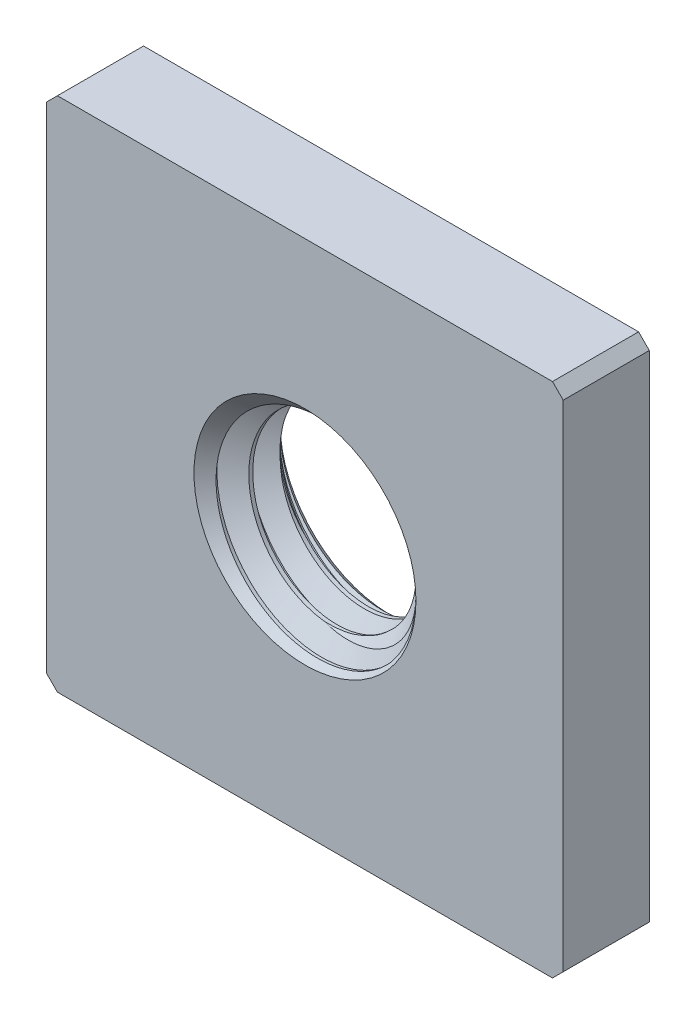
SolidWorks part; units mm, degrees
ref_plane "Front Plane" through (0, 0, 0) normal (0, 0, 1) x (1, 0, 0)
ref_plane "Top Plane" through (0, 0, 0) normal (0, 1, 0) x (1, 0, 0)
ref_plane "Right Plane" through (0, 0, 0) normal (1, 0, 0) x (0, 0, -1)
sketch "Sketch1" plane through (0, 0, 0) normal (0, 0, 1) x (1, 0, 0)
  line L1 (19.05, 19.05) -> (-19.05, 19.05) construction
  line L2 (19.05, 19.05) -> (19.05, -19.05) construction
  line L3 (19.05, -19.05) -> (-19.05, -19.05) construction
  line L4 (-19.05, 19.05) -> (-19.05, -19.05) construction
  line L5 (19.05, 19.05) -> (-19.05, -19.05) construction
  line L6 (19.05, -19.05) -> (-19.05, 19.05) construction
  point P0 (0, 0)
  dimension "For Leg Outer Length" = 38.1
  dimension "For Leg Outer Width" = 38.1
sketch "Sketch2" plane through (0, 0, 0) normal (0, 1, 0) x (1, 0, 0)
  line L0 (0, 3.175) -> (0, -3.175) construction
  line L2 (7.9375, -3.175) -> (-7.9375, -3.175) construction
  line L3 (-19.05, 3.175) -> (19.05, 3.175) construction
  line L4 (-19.05, -3.175) -> (19.05, -3.175) construction
  line L6 (8.1875, -3.0307) -> (8.1875, -5.3398) construction
  line L7 (8.1875, -5.3398) -> (6.1877, -4.1852) construction
  line L8 (6.1877, -4.1852) -> (8.1875, -3.0307) construction
  line L9 (6.1877, -4.1852) -> (6.4377, -4.1852) construction
  line L10 (8.1875, -4.1852) -> (7.9375, -4.1852) construction
  line L11 (6.4377, -4.3295) -> (6.4377, -4.0409) construction
  line L12 (7.9375, -5.1955) -> (7.9375, -3.175) construction
  line L13 (8.0625, -5.2676) -> (8.0625, -3.1028) construction
  point P4 (0, 0)
  point P8 (0, -3.175)
  point P11 (0, 3.175)
  point P14 (0, -3.175)
  point P26 (6.4377, -4.1852)
  point P29 (7.9375, -4.1852)
  point P32 (8.0625, -4.1852)
  dimension "Thread Diameter" = 15.875
  dimension "Height" = 6.35
  dimension "Thread Pitch" = 2.3091
  dimension "D1" = 0.2886
sketch "Sketch3" plane through (0, 0, 0) normal (0, 0, 1) x (1, 0, 0)
  line L0 (-19.05, 0) -> (19.05, 0) construction
  line L1 (19.05, 19.05) -> (-19.05, 19.05)
  line L2 (19.05, 19.05) -> (19.05, -19.05)
  line L3 (19.05, -19.05) -> (-19.05, -19.05)
  line L4 (-19.05, 19.05) -> (-19.05, -19.05)
  line L5 (19.05, 19.05) -> (-19.05, -19.05) construction
  line L6 (19.05, -19.05) -> (-19.05, 19.05) construction
  circle A0 centre (0, 0) radius 7.9375
  point P0 (0, 0)
extrude "Boss-Extrude1" add sketch "Sketch3" against normal up to vertex (3.175 mm away) from vertex up to point (0, 0, -3.175) starting at point (0, 0, 3.175)
chamfer "Chamfer1" distance 0.7937 angle 45 4 edges at (-19.05, 19.05, 0) (19.05, 19.05, 0) (19.05, -19.05, 0) (-19.05, -19.05, 0)
sketch "Sketch4" plane through (0, 0, 3.175) normal (0, 0, 1) x (1, 0, 0)
  circle A0 centre (0, 0) radius 7.9375 construction
  circle A1 centre (0, 0) radius 7.9375
curve "Helix/Spiral1" pitch 2.3091 height 8.6591 radius 7.9375 centre (0, 0, 3.175) axis (0, 0, -1) start towards (1, 0, 0)
sketch "Sketch5" plane through (0, 0, 0) normal (0, 1, 0) x (1, 0, 0)
  line L0 (8.0625, -3.1028) -> (8.0625, -5.2676)
  line L1 (8.0625, -5.2676) -> (6.4377, -4.3295)
  line L2 (6.4377, -4.3295) -> (6.4377, -4.0409)
  line L3 (6.4377, -4.0409) -> (8.0625, -3.1028)
sweep "Sweep1" add profiles "Sketch5" path "Helix/Spiral1"
sketch "Sketch6" plane through (0, 0, 3.175) normal (0, 0, 1) x (1, 0, 0)
  circle A0 centre (0, 0) radius 8.1875
extrude "Cut-Extrude1" cut sketch "Sketch6" against normal through all draft 45 and the other way through all
extrude "Cut-Extrude2" cut sketch "Sketch6<2>" against normal through all and the other way through all draft 45 from surface starting at face at (0, 0, -3.175)
sketch "Sketch6<2>" plane through (0, 0, 3.175) normal (0, 0, 1) x (1, 0, 0) same geometry as "Sketch6"
equation "\"D1@Sketch2\"=\"Thread Pitch@Sketch2\"/8"
equation "\"D4@Helix/Spiral1\"=\"Thread Pitch@Sketch2\""
equation "\"D3@Helix/Spiral1\"=\"Height@Sketch2\"+\"Thread Pitch@Sketch2\""
